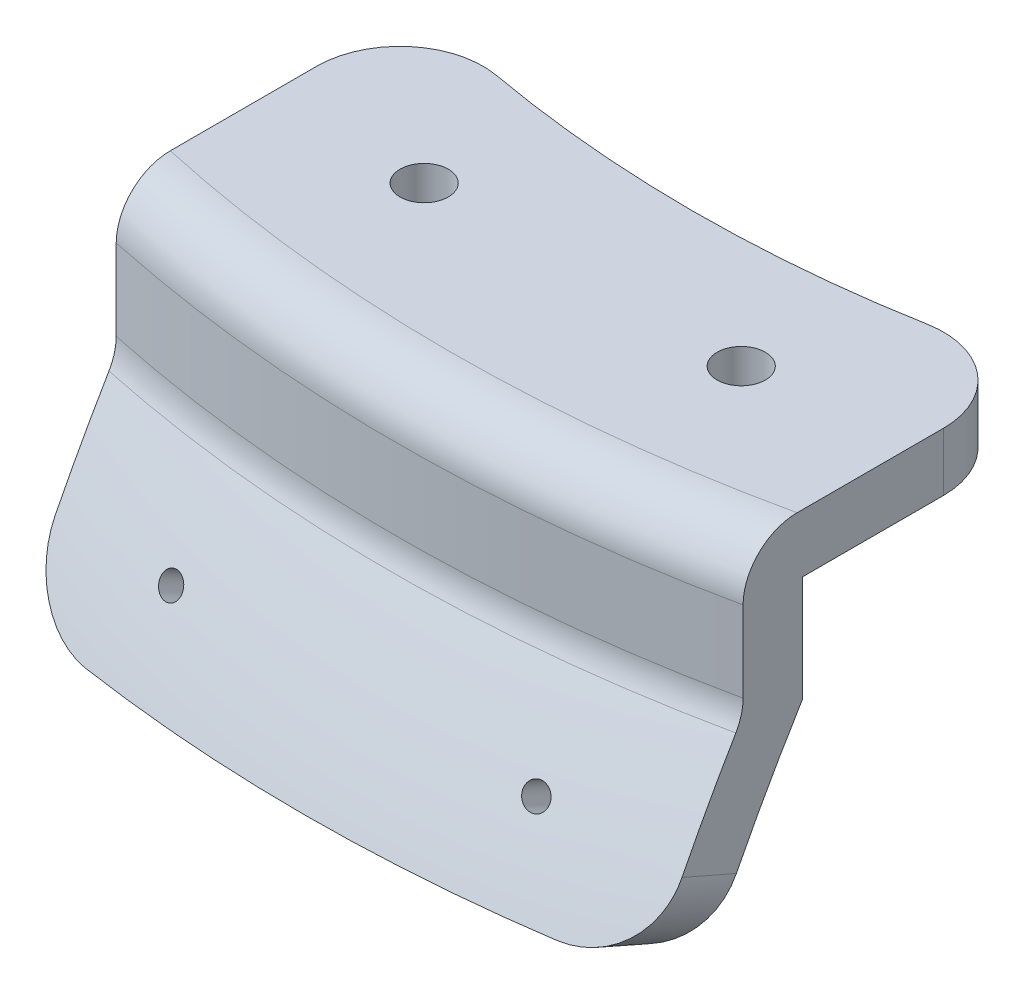
SolidWorks part; units mm, degrees
material "Polyether Polyol"
ref_plane "Front Plane" through (0, 0, 0) normal (0, 0, 1) x (1, 0, 0)
ref_plane "Top Plane" through (0, 0, 0) normal (0, 1, 0) x (1, 0, 0)
ref_plane "Right Plane" through (0, 0, 0) normal (1, 0, 0) x (0, 0, -1)
sketch "Sketch2" plane through (0, 0, 0) normal (1, 0, 0) x (0, 0, -1)
  line L0 (-174.1012, 209.4005) -> (-174.1012, 196.7005) construction
  line L1 (-192.235, 176.9476) -> (-185.8333, 174.116) construction
  line L2 (-181.1012, 216.4005) -> (-181.1012, 198.6268) construction
  line L3 (-181.1012, 216.4005) -> (-145.5262, 216.4005) construction
  line L4 (-145.5262, 216.4005) -> (-145.5262, 209.4005) construction
  line L5 (-145.5262, 209.4005) -> (-174.1012, 209.4005) construction
  line L12 (0, 91.9198) -> (0, 209.4005) construction
  line L13 (-174.1012, 209.4005) -> (-174.1012, 196.7005)
  line L14 (-192.235, 176.9476) -> (-185.8333, 174.116)
  line L15 (-181.1012, 216.4005) -> (-181.1012, 198.6268)
  line L16 (-181.1012, 216.4005) -> (-145.5262, 216.4005)
  line L17 (-145.5262, 216.4005) -> (-145.5262, 209.4005)
  line L18 (-145.5262, 209.4005) -> (-174.1012, 209.4005)
  arc A0 (-174.1012, 196.7005) -> (-185.8333, 174.116) centre (0, 91.9198) ccw construction
  arc A1 (-181.1012, 198.6268) -> (-192.235, 176.9476) centre (0, 91.9198) ccw construction
  arc A4 (-174.1012, 196.7005) -> (-185.8333, 174.116) centre (0, 91.9198) ccw
  arc A5 (-181.1012, 198.6268) -> (-192.235, 176.9476) centre (0, 91.9198) ccw
revolve "Revolve1" add sketch "Sketch2" angle 30 mid plane about L12
fillet "Fillet1" radius 6.35 2 edges at (0, 198.6268, 181.1012) (0, 216.4005, 181.1012)
sketch "Sketch3" plane through (0, 216.4005, 0) normal (0, -1, 0) x (1, 0, 0)
  circle A2 centre (-19.05, 158.75) radius 3.5719 construction
  circle A3 centre (19.05, 158.75) radius 3.5719 construction
  circle A4 centre (19.05, 158.75) radius 2.9
  circle A5 centre (-19.05, 158.75) radius 2.9
  dimension "D1" = 5.8
extrude "Cut-Extrude1" cut sketch "Sketch3" along normal through all contours A4 | A5 region at (19.05, 216.4005, 158.75) region at (-19.05, 216.4005, 158.75)
sketch "Sketch4" plane through (0, 216.4005, 0) normal (0, 1, 0) x (1, 0, 0)
  line L0 (37.665, -140.5675) -> (45.2289, -168.7967) construction
  line L1 (37.665, -140.5675) -> (-37.665, -140.5675)
  line L2 (37.665, -140.5675) -> (37.665, -192.235)
  line L3 (37.665, -192.235) -> (-37.665, -192.235)
  line L4 (-37.665, -140.5675) -> (-37.665, -192.235)
  line L5 (-37.665, -140.5675) -> (-45.2289, -168.7967) construction
  arc A0 (-37.665, -140.5675) -> (37.665, -140.5675) centre (0, 0) ccw construction
  arc A1 (-49.7541, -185.6848) -> (49.7541, -185.6848) centre (0, 0) ccw construction
extrude "Cut-Extrude2" cut sketch "Sketch4" against normal through all flip side to cut
fillet "Fillet2" radius 10 4 edges at (-37.665, 212.9005, 140.5675) (37.665, 212.9005, 140.5675)
sketch "Sketch5" plane through (0, 0, 0) normal (-1, 0, 0) x (0, 0, 1)
  line L0 (0, 91.9198) -> (181.0525, 184.1706) construction
  line L2 (0, -200000) -> (0, 218797.9879) construction
  arc A0 (185.8333, 174.116) -> (174.1012, 196.7005) centre (0, 91.9198) ccw construction
  dimension "D1" = 63
ref_plane "Plane1" through (0, 72.9744, -37.1823) normal (0, 0.891, -0.454) x (0, 0.454, 0.891)
sketch "Sketch6" plane through (0, 72.9744, -37.1823) normal (0, 0.891, -0.454) x (0, 0.454, 0.891)
  line L0 (217.8481, 19.0592) -> (275.7942, 24.1289) construction
  line L2 (217.8481, 19.0592) -> (275.7942, 24.1289)
  line L3 (217.8481, 19.0592) -> (217.7174, 20.5535)
  line L4 (275.7942, 24.1289) -> (275.6635, 25.6232)
  line L5 (217.7174, 20.5535) -> (275.6635, 25.6232)
  line L6 (41.7307, 0) -> (244.9307, 0) construction
  ellipse E0 centre (89.3002, 0) end of major axis (89.3002, 145.5262) minor radius 129.6648 construction
  dimension "D1" = 5
  dimension "D2" = 1.5
revolve "Cut-Revolve1" cut sketch "Sketch6" angle 360 about L0
mirror "Mirror1" about plane through (0, 0, 0) normal (1, 0, 0) of "Cut-Revolve1"
